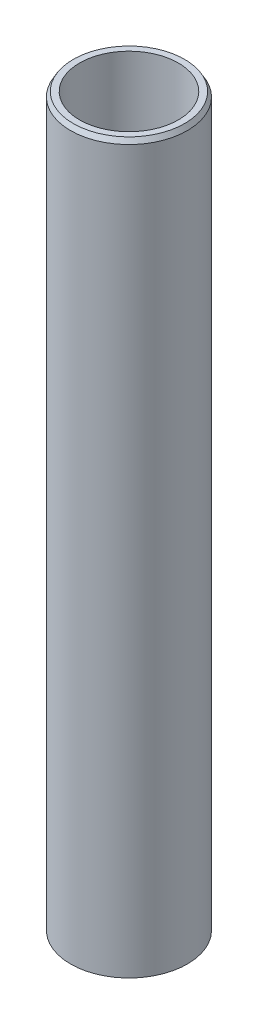
SolidWorks part; units mm, degrees
ref_plane "Front Plane" through (0, 0, 0) normal (0, 0, 1) x (1, 0, 0)
ref_plane "Top Plane" through (0, 0, 0) normal (0, 1, 0) x (1, 0, 0)
ref_plane "Right Plane" through (0, 0, 0) normal (1, 0, 0) x (0, 0, -1)
sketch "Sketch1" plane through (0, 0, 0) normal (0, 1, 0) x (1, 0, 0)
  circle A0 centre (0, 0) radius 35
  dimension "SHAFT_OD" = 70
extrude "Boss-Extrude1" add sketch "Sketch1" along normal blind 437.1118
sketch "Sketch2" plane through (0, 0, 0) normal (0, 1, 0) x (1, 0, 0)
  circle A0 centre (0, 0) radius 29.5936
  dimension "BORE_D" = 59.1873
extrude "Cut-Extrude1" cut sketch "Sketch2" along normal through all
chamfer "Chamfer1" distance 2.8315 angle 30 2 edges at (0, 437.1118, 35) (0, 0, 35) first distance on face at (0, 437.1118, 35) first distance on face at (0, 0, 29.5936)
